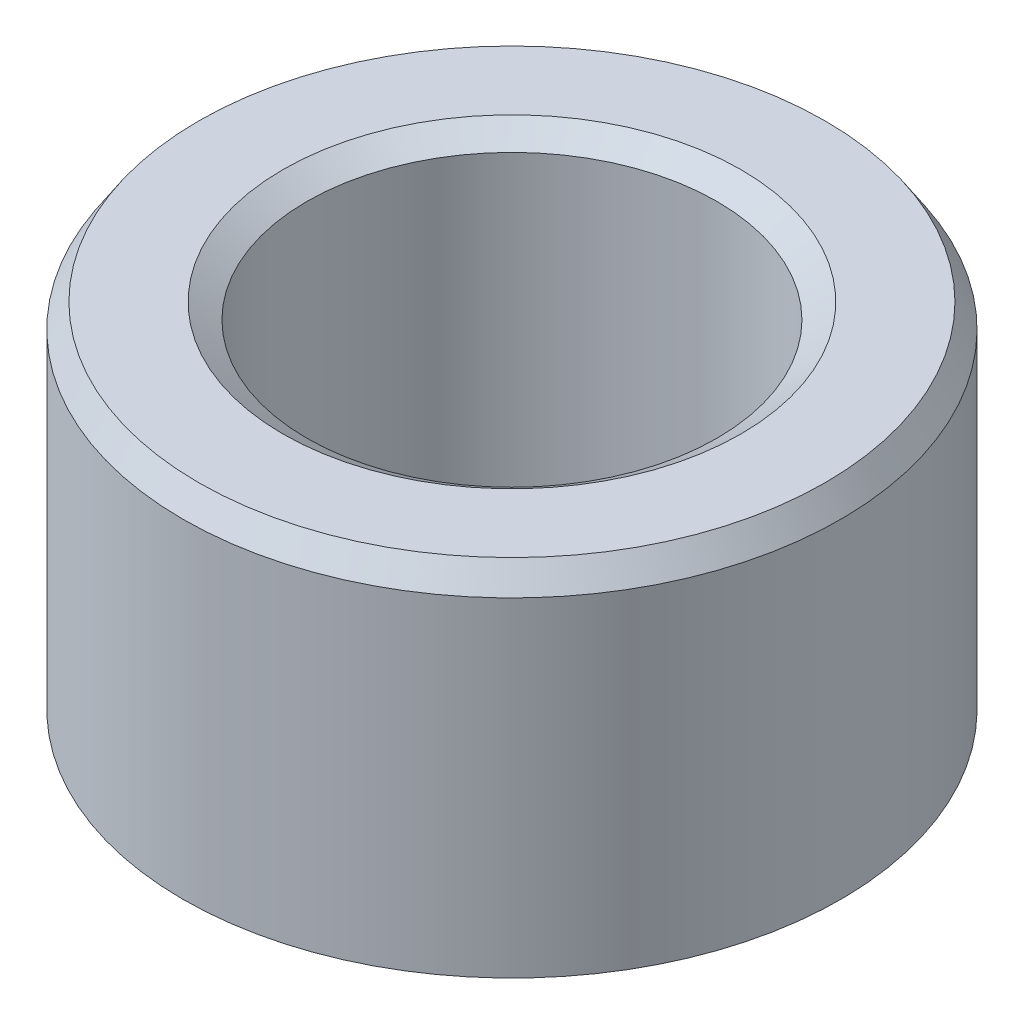
SolidWorks part; units mm, degrees
ref_plane "Front Plane" through (0, 0, 0) normal (0, 0, 1) x (1, 0, 0)
ref_plane "Top Plane" through (0, 0, 0) normal (0, 1, 0) x (1, 0, 0)
ref_plane "Right Plane" through (0, 0, 0) normal (1, 0, 0) x (0, 0, -1)
sketch "Sketch1" plane through (0, 0, 0) normal (0, 1, 0) x (1, 0, 0)
  circle A0 centre (0, 0) radius 47.5
  dimension "SLEEVE_OD" = 95
extrude "Boss-Extrude1" add sketch "Sketch1" along normal blind 53.2531
sketch "Sketch2" plane through (0, 0, 0) normal (0, 1, 0) x (1, 0, 0)
  circle A0 centre (0, 0) radius 29.6193
  dimension "BORE_D" = 59.2386
extrude "Cut-Extrude1" cut sketch "Sketch2" along normal through all
chamfer "Chamfer1" distance 3.4536 angle 33.143 4 edges at (0, 53.2531, 29.6193) (0, 0, 29.6193) (0, 0, 47.5) (0, 53.2531, 47.5) first distance on face at (0, 53.2531, 29.6193) first distance on face at (0, 0, 29.6193) first distance on face at (0, 53.2531, 47.5)
